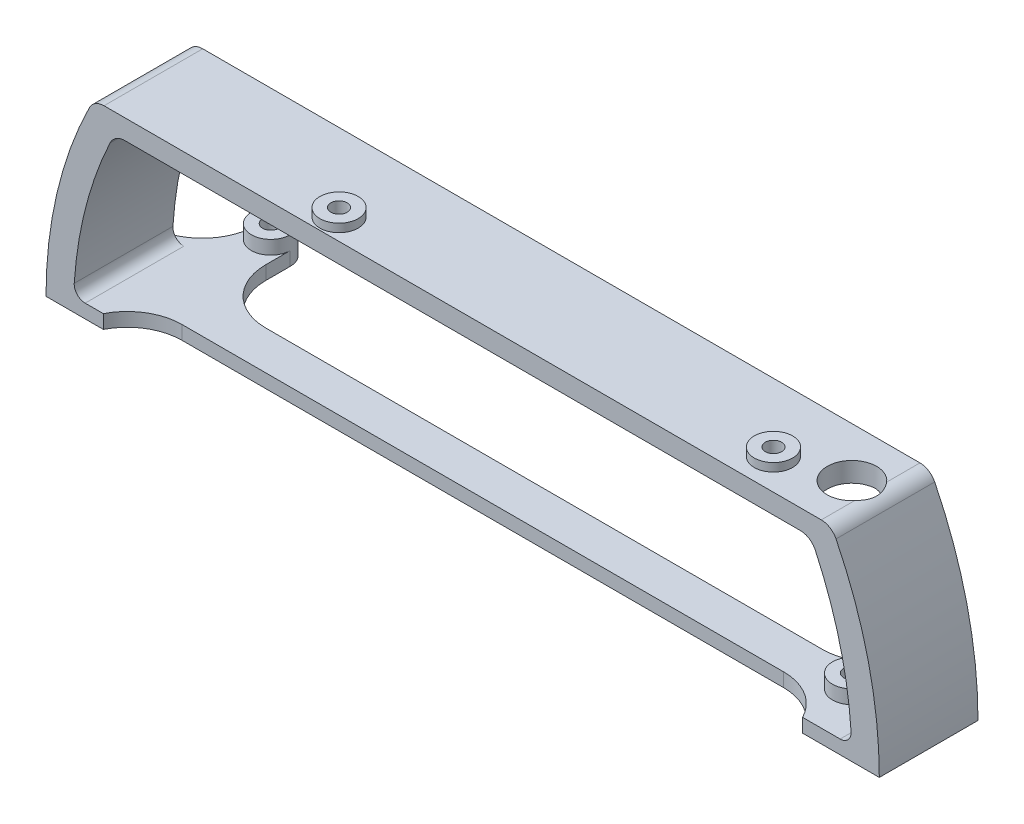
SolidWorks part; units mm, degrees
ref_plane "Front Plane" through (0, 0, 0) normal (0, 0, 1) x (1, 0, 0)
ref_plane "Top Plane" through (0, 0, 0) normal (0, 1, 0) x (1, 0, 0)
ref_plane "Right Plane" through (0, 0, 0) normal (1, 0, 0) x (0, 0, -1)
sketch "Sketch1" plane through (0, 0, 0) normal (0, 1, 0) x (1, 0, 0)
  line L0 (0, 0) -> (-78.74, 0) construction
  line L1 (-78.74, 0) -> (-78.74, 22.86) construction
  circle A0 centre (78.74, 0) radius 4.5
  circle A3 centre (-78.74, 22.86) radius 4.5
  dimension "D2" = 9
  dimension "D3" = 78.74
  dimension "D4" = 22.86
  dimension "D5" = 78.74
extrude "Boss-Extrude1" add sketch "Sketch1" along normal blind 6.35
sketch "Sketch2" plane through (0, 0, 0) normal (0, 1, 0) x (1, 0, 0)
  line L0 (-83.24, 22.86) -> (-83.24, -4.5)
  line L1 (-83.24, -4.5) -> (78.74, -4.5)
  line L2 (-74.24, 22.86) -> (-74.24, 4.5)
  line L3 (-74.24, 4.5) -> (78.74, 4.5)
  circle A0 centre (-78.74, 22.86) radius 4.5 construction
  circle A1 centre (78.74, 0) radius 4.5 construction
  circle A2 centre (-78.74, 22.86) radius 4.5
  circle A3 centre (78.74, 0) radius 4.5
extrude "Boss-Extrude2" add sketch "Sketch2" along normal blind 3.175 contours A3 L3 L2 A2 L0 L1
sketch "Sketch5" plane through (0, 0, 0) normal (0, 0, 1) x (1, 0, 0)
  line L0 (83.24, 0) -> (96.52, 0)
  line L1 (83.24, 3.175) -> (90.1141, 3.175)
  line L2 (83.24, 0) -> (83.24, 6.35) construction
  line L3 (0, 90.17) -> (0, 0) construction
  line L4 (-83.24, 3.175) -> (-90.1141, 3.175)
  line L5 (-83.24, 0) -> (-96.52, 0)
  line L6 (83.24, 3.175) -> (83.24, 0)
  line L7 (-87.6646, 40.386) -> (87.6646, 40.386)
  line L8 (-83.24, 3.175) -> (-83.24, 0)
  line L9 (78.74, 3.175) -> (78.74, 0) construction
  line L10 (78.74, 3.175) -> (83.24, 3.175)
  line L11 (78.74, 3.175) -> (78.74, 0)
  line L12 (78.74, 0) -> (83.24, 0)
  line L13 (83.24, 3.175) -> (83.24, 0)
  line L14 (-85.4101, 44.958) -> (85.4101, 44.958)
  line L16 (-74.24, 6.35) -> (-83.24, 6.35) construction
  arc A0 (96.52, 0) -> (-96.52, 0) centre (0, 0) ccw
  arc A1 (90.1141, 3.175) -> (-90.1141, 3.175) centre (0, 0) ccw
  circle A3 centre (0, 0) radius 96.52 construction
  circle A4 centre (0, 0) radius 90.17 construction
  point P5 (92.4725, 0)
  point P17 (93.2134, 28.4982)
  dimension "D1" = 193.04
  dimension "D3" = 4.572
  dimension "D4" = 38.608
  dimension "D2" = 6.35
extrude "Boss-Extrude3" add sketch "Sketch5" along normal mid plane 22.86 contours A1 L7 A0 L5 L8 L4 | A1 L14 A0 L7 | L7 A1 L14 | L11 L12 L6 L10 | A1 L1 L6 L0 A0 L7 | A1 L7 A0 L14
sketch "Sketch6" plane through (0, 0, 0) normal (0, -1, 0) x (1, 0, 0)
  point P0 (-78.74, -22.86)
  point P1 (78.74, 0)
hole_wizard "#6 Clearance Hole1" positions "3DSketch2" profile "Sketch8" hole size "#6" standard "ANSI Inch" end condition through all
sketch3d "3DSketch2"
  point P0 (-78.74, 0, -22.86)
  point P3 (78.74, 0, 0)
sketch "Sketch8" plane through (-78.74, 0, -22.86) normal (1, 0, 0) x (0, 0, -1)
  line L0 (0, 0) -> (0, 44.958)
  line L1 (0, 44.958) -> (1.8986, 44.958)
  line L2 (1.8986, 44.958) -> (1.8986, 0)
  line L5 (1.8986, 0) -> (0, 0)
  line L11 (0, -6.35) -> (0, 107.95) construction
  dimension "Thru Hole Dia." = 3.7973
  dimension "Thru Hole Depth" = 44.958
sketch "Sketch9" plane through (0, 44.958, 0) normal (0, 1, 0) x (1, 0, 0)
  point P0 (64.8223, -4.2545)
  point P1 (-33.5265, -6.5405)
fillet "Fillet1" radius 2.54 2 edges at (90.1141, 3.175, 0) (-90.1141, 3.175, 0)
fillet "Fillet2" radius 3.81 5 edges at (80.6201, 40.386, -5.8474) (80.6201, 40.386, 5.8474) (-80.6201, 40.386, 0) (-85.4101, 44.958, 0) (85.4101, 44.958, 0)
fillet "Fillet3" radius 12.7 5 edges at (78.74, 1.5875, -4.5) (78.74, 1.5875, 4.5) (-74.24, 1.5875, -4.5) (-83.24, 1.5875, -11.43) (-83.24, 1.5875, 4.5)
sketch "Sketch10" plane through (0, 44.958, 0) normal (0, 1, 0) x (1, 0, 0)
  circle A0 centre (78.74, 0) radius 5.715
  dimension "D1" = 11.43
extrude "Cut-Extrude1" cut sketch "Sketch10" against normal up to surface (38.608 mm away) up to face at (78.74, 6.35, 1.8986)
hole_wizard "#6 Clearance Hole2" positions "3DSketch3" profile "Sketch12" hole size "#6" standard "ANSI Inch"
sketch3d "3DSketch3"
  point P0 (-33.5265, 44.958, 6.5405)
  point P3 (64.8223, 44.958, 4.2545)
sketch "Sketch12" plane through (-33.5265, 44.958, 6.5405) normal (1, 0, 0) x (0, 0, 1)
  line L0 (0, 0) -> (0, 5.7118)
  line L1 (0, 5.7118) -> (1.8986, 4.571)
  line L2 (1.8986, 4.571) -> (1.8986, 0)
  line L5 (1.8986, 0) -> (0, 0)
  line L10 (0, 5.7118) -> (-1.8987, 4.571) construction
  line L11 (0, -6.35) -> (0, 107.95) construction
  dimension "Hole Dia." = 3.7973
  dimension "Hole Depth" = 4.571
  dimension "Drill Angle" = 118
sketch "Sketch13" plane through (0, 44.958, 0) normal (0, 1, 0) x (1, 0, 0)
  circle A0 centre (64.8223, -4.2545) radius 1.8987 construction
  circle A1 centre (-33.5265, -6.5405) radius 1.8987 construction
  circle A2 centre (64.8223, -4.2545) radius 1.8987
  circle A3 centre (-33.5265, -6.5405) radius 1.8986
  circle A4 centre (-33.5265, -6.5405) radius 4.4386
  circle A5 centre (64.8223, -4.2545) radius 4.4387
  dimension "D1" = 2.54
extrude "Boss-Extrude5" add sketch "Sketch13" along normal blind 1.912
equation "\"7.6n\"=7.675"
